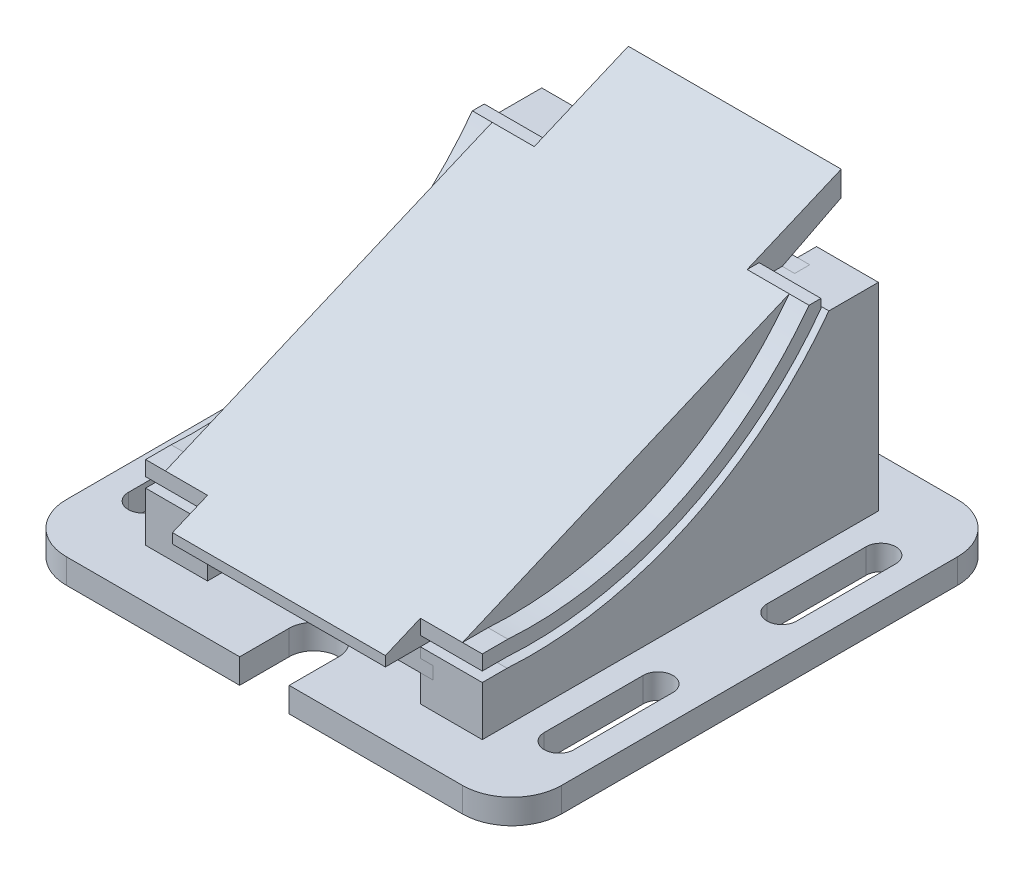
SolidWorks part; units mm, degrees
other "prensa"
other "base_prensa"
material "Aleación 1060"
ref_plane "Alzado" through (0, 0, 0) normal (0, 0, 1) x (1, 0, 0)
ref_plane "Planta" through (0, 0, 0) normal (0, 1, 0) x (1, 0, 0)
ref_plane "Vista lateral" through (0, 0, 0) normal (1, 0, 0) x (0, 0, -1)
sketch "Croquis2" plane through (0, 0, 0) normal (0, 1, 0) x (1, 0, 0)
  line L1 (50, -50) -> (-50, -50)
  line L2 (50, -50) -> (50, 50)
  line L3 (50, 50) -> (-50, 50)
  line L4 (-50, -50) -> (-50, 50)
  line L5 (50, -50) -> (-50, 50) construction
  line L6 (50, 50) -> (-50, -50) construction
  point P0 (0, 0)
  dimension "D1" = 100
  dimension "D2" = 100
extrude "Saliente-Extruir1" add sketch "Croquis2" along normal blind 5
fillet "Redondeo1" radius 10 4 edges at (-50, 2.5, -50) (50, 2.5, -50) (-50, 2.5, 50) (50, 2.5, 50)
sketch "Croquis3" plane through (0, 5, 0) normal (0, 1, 0) x (1, 0, 0)
  line L0 (-40, -50) -> (40, -50) construction
  line L1 (-5, -50) -> (5, -50)
  line L2 (-5, -50) -> (-5, -40)
  line L4 (5, -50) -> (5, -40)
  line L5 (-42, 32.5) -> (-42, 12.5) construction
  line L6 (-39, 32.5) -> (-39, 12.5)
  line L7 (-45, 32.5) -> (-45, 12.5)
  line L8 (42, 32.5) -> (42, 12.5) construction
  line L9 (45, 32.5) -> (45, 12.5)
  line L10 (39, 32.5) -> (39, 12.5)
  line L11 (-42, -12.5) -> (-42, -32.5) construction
  line L12 (-39, -12.5) -> (-39, -32.5)
  line L13 (-45, -12.5) -> (-45, -32.5)
  line L14 (42, -12.5) -> (42, -32.5) construction
  line L15 (45, -12.5) -> (45, -32.5)
  line L16 (39, -12.5) -> (39, -32.5)
  line L18 (-50, 40) -> (-50, -40) construction
  line L19 (50, -40) -> (50, 40) construction
  line L20 (0, 20.2073) -> (-17.5, 10.1036)
  line L21 (-17.5, 10.1036) -> (-17.5, -10.1036)
  line L22 (-17.5, -10.1036) -> (0, -20.2073)
  line L23 (0, -20.2073) -> (17.5, -10.1036)
  line L24 (17.5, -10.1036) -> (17.5, 10.1036)
  line L25 (17.5, 10.1036) -> (0, 20.2073)
  arc A0 (5, -40) -> (-5, -40) centre (0, -40) ccw
  arc A1 (-39, 32.5) -> (-45, 32.5) centre (-42, 32.5) ccw
  arc A2 (-45, 12.5) -> (-39, 12.5) centre (-42, 12.5) ccw
  arc A3 (45, 32.5) -> (39, 32.5) centre (42, 32.5) ccw
  arc A4 (39, 12.5) -> (45, 12.5) centre (42, 12.5) ccw
  arc A5 (-39, -12.5) -> (-45, -12.5) centre (-42, -12.5) ccw
  arc A6 (-45, -32.5) -> (-39, -32.5) centre (-42, -32.5) ccw
  arc A7 (45, -12.5) -> (39, -12.5) centre (42, -12.5) ccw
  arc A8 (39, -32.5) -> (45, -32.5) centre (42, -32.5) ccw
  circle A9 centre (0, 0) radius 17.5 construction
  point P10 (-42, 22.5)
  point P15 (42, 22.5)
  point P22 (-42, -22.5)
  point P29 (42, -22.5)
  dimension "D2" = 5
  dimension "D5" = 3
  dimension "D10" = 35
  dimension "D1" = 10
  dimension "D3" = 22.5
  dimension "D4" = 5
  dimension "D6" = 20
  dimension "D7" = 5
  dimension "D8" = 45
  dimension "D9" = 20
extrude "Cortar-Extruir1" cut sketch "Croquis3" against normal blind 5
sketch "Croquis4" plane through (0, 5, 0) normal (0, 1, 0) x (1, 0, 0)
  line L0 (-39, 12.5) -> (-39, 32.5) construction
  line L1 (-34, 40) -> (-24, 40)
  line L2 (-34, 40) -> (-34, -40)
  line L3 (-34, -40) -> (-24, -40)
  line L4 (-24, 40) -> (-24, -40)
  line L5 (24, 40) -> (34, 40)
  line L6 (24, 40) -> (24, -40)
  line L7 (24, -40) -> (34, -40)
  line L8 (34, 40) -> (34, -40)
  line L9 (39, 32.5) -> (39, 12.5) construction
  point P8 (-24, 0)
  point P10 (24, 0)
  dimension "D1" = 10
  dimension "D2" = 10
  dimension "D3" = 5
  dimension "D4" = 5
  dimension "D5" = 80
extrude "Saliente-Extruir2" add sketch "Croquis4" along normal blind 40
sketch "Croquis5" plane through (34, 0, 0) normal (1, 0, 0) x (0, 0, -1)
  line L1 (-40, 5) -> (40, 5) construction
  line L5 (-40, 15) -> (-35, 15)
  line L7 (-40, 45) -> (40, 45) construction
  line L8 (-40, 15) -> (-40, 45)
  line L9 (-40, 45) -> (30, 45)
  line L11 (40, 45) -> (40, 5) construction
  arc A0 (-35, 15) -> (30, 45) centre (-30.1189, 89.841) ccw
  dimension "D4" = 75
  dimension "D1" = 10
  dimension "D2" = 5
  dimension "D3" = 10
extrude "Cortar-Extruir2" cut sketch "Croquis5" against normal blind 84
sketch "Croquis8" plane through (-24, 0, 0) normal (1, 0, 0) x (0, 0, -1)
  line L0 (30, 45) -> (40, 45) construction
  line L1 (-40, 15) -> (-40, 5) construction
  line L2 (-40, 12.9735) -> (-40, 15)
  line L3 (33.0913, 45) -> (30, 45)
  line L5 (-40, 15) -> (-35, 15)
  arc A1 (-35, 15) -> (30, 45) centre (-30.1189, 89.841) ccw construction
  arc A2 (-35.1627, 12.5053) -> (32.004, 43.5053) centre (-30.1189, 89.841) ccw
  arc A3 (-40, 12.9735) -> (33.0913, 45) centre (-30.1189, 89.841) ccw
  arc A4 (-35, 15) -> (30, 45) centre (-30.1189, 89.841) ccw
  dimension "D1" = 2.5
extrude "Saliente-Extruir4" add sketch "Croquis8" along normal blind 2.5
sketch "Croquis9" plane through (-24, 0, 0) normal (1, 0, 0) x (0, 0, -1)
  line L1 (33.0913, 45) -> (40, 45) construction
  line L2 (-40, 12.9735) -> (-40, 5) construction
  line L3 (-40, 10.4536) -> (-40, 5)
  line L4 (-40, 5) -> (40, 5)
  line L5 (40, 5) -> (40, 45)
  line L6 (40, 45) -> (36.1328, 45)
  arc A2 (-40.3187, 10.4939) -> (35.1304, 43.5535) centre (-30.1189, 89.841) ccw
  arc A3 (-40, 10.4536) -> (36.1328, 45) centre (-30.1189, 89.841) ccw
  dimension "D1" = 2.5
extrude "Saliente-Extruir5" add sketch "Croquis9" along normal blind 2.5
mirror "Simetría1" about plane through (0, 0, 0) normal (1, 0, 0) of "Saliente-Extruir4", "Saliente-Extruir5"
sketch "Croquis10" plane through (0, 0, 0) normal (1, 0, 0) x (0, 0, -1)
  line L4 (-40, 20) -> (-34.8343, 20)
  line L5 (-40, 17) -> (-34.9344, 17)
  line L6 (-40, 17) -> (-34.9344, 17)
  line L7 (-40, 20) -> (-40, 17)
  line L8 (28.3968, 46.1958) -> (28.3968, 47.9894)
  line L9 (28.3968, 47.9894) -> (25.9921, 47.9894)
  arc A4 (-34.8343, 20) -> (25.9921, 47.9894) centre (-30.1189, 89.841) ccw
  arc A5 (-34.9344, 17) -> (28.3968, 46.1958) centre (-30.1189, 89.841) ccw
  arc A6 (-34.9344, 17) -> (28.3968, 46.1958) centre (-30.1189, 89.841) ccw
  dimension "D1" = 2
  dimension "D2" = 3
extrude "Saliente-Extruir6" add sketch "Croquis10" against normal up to vertex (34 mm away) and the other way up to vertex (34 mm away) separate body up to point (-34, 15, 35) other way up to point (34, 15, 35)
sketch "Croquis11" plane through (0, 0, 0) normal (1, 0, 0) x (0, 0, -1)
  line L0 (-40, 20) -> (25.9921, 47.9894)
  line L1 (-34.8343, 20) -> (-40, 20) construction
  line L2 (-34.8343, 20) -> (-40, 20)
  arc A0 (-34.8343, 20) -> (25.9921, 47.9894) centre (-30.1189, 89.841) ccw construction
  arc A1 (-34.8343, 20) -> (25.9921, 47.9894) centre (-30.1189, 89.841) ccw
extrude "Saliente-Extruir7" add sketch "Croquis11" along normal blind 30 and the other way blind 30
sketch "Croquis12" plane through (-24, 0, 0) normal (1, 0, 0) x (0, 0, -1)
  line L2 (36.1328, 45) -> (33.0913, 45)
  line L3 (-40, 12.9735) -> (-40, 10.4536)
  line L4 (36.1328, 45) -> (33.0913, 45)
  line L5 (-40, 12.9735) -> (-40, 10.4536)
  arc A2 (-40, 10.4536) -> (36.1328, 45) centre (-30.1189, 89.841) ccw
  arc A3 (-40, 12.9735) -> (33.0913, 45) centre (-30.1189, 89.841) ccw
  arc A4 (-40, 10.4536) -> (36.1328, 45) centre (-30.1189, 89.841) ccw
  arc A5 (-40, 12.9735) -> (33.0913, 45) centre (-30.1189, 89.841) ccw
  dimension "D1" = 0
extrude "Saliente-Extruir8" add sketch "Croquis12" along normal up to vertex (48 mm away) separate body up to point (24, 45, -36.1328)
sketch "Croquis15" plane through (0, 0, 0) normal (1, 0, 0) x (0, 0, -1)
  line L0 (-40, 17) -> (-34.9344, 17) construction
  line L1 (-40, 17) -> (-34.9344, 17)
  line L2 (-40, 12.9735) -> (-40, 17)
  line L3 (33.0913, 45) -> (33.0913, 46.1958)
  line L4 (33.0913, 46.1958) -> (28.3968, 46.1958)
  arc A0 (-40, 12.9735) -> (33.0913, 45) centre (-30.1189, 89.841) ccw construction
  arc A1 (-34.9344, 17) -> (28.3968, 46.1958) centre (-30.1189, 89.841) ccw construction
  arc A2 (-40, 12.9735) -> (33.0913, 45) centre (-30.1189, 89.841) ccw
  arc A3 (-34.9344, 17) -> (28.3968, 46.1958) centre (-30.1189, 89.841) ccw
extrude "Saliente-Extruir9" add sketch "Croquis15" along normal mid plane 43
sketch "Croquis16" plane through (0, 0, 0) normal (1, 0, 0) x (0, 0, -1)
  line L0 (-47.0733, 17) -> (44.9886, 56.0464)
  line L2 (25.9921, 47.9894) -> (-40, 20) construction
  line L3 (-40, 17) -> (-34.9344, 17) construction
  line L4 (-40, 17) -> (-34.9344, 17)
  line L5 (-40, 17) -> (-47.0733, 17)
  line L7 (28.3968, 46.1958) -> (33.0913, 46.1958)
  line L8 (33.0913, 46.1958) -> (44.9886, 56.0464)
  arc A0 (-34.9344, 17) -> (28.3968, 46.1958) centre (-30.1189, 89.841) ccw construction
  arc A1 (-34.9344, 17) -> (28.3968, 46.1958) centre (-30.1189, 89.841) ccw
  point P3 (-1.0424, 36.5232)
  dimension "D1" = 100
extrude "Saliente-Extruir10" add sketch "Croquis16" along normal mid plane 43
sketch "Croquis18" plane through (-21.5, 0, 0) normal (-1, 0, 0) x (0, 0, 1)
  line L0 (-44.9886, 56.0464) -> (-44.9886, 51.0464)
  line L1 (-44.9886, 51.0464) -> (-33.0913, 45)
  line L2 (-33.0913, 45) -> (-33.0913, 46.1958)
  line L3 (-33.0913, 46.1958) -> (-44.9886, 56.0464)
  line L4 (40, 15) -> (47.0733, 15)
  line L5 (47.0733, 15) -> (47.0733, 17)
  line L6 (47.0733, 17) -> (40, 17)
  line L7 (40, 17) -> (40, 15)
  point P10 (47.0733, 15)
  dimension "D1" = 5
extrude "Saliente-Extruir12" add sketch "Croquis18" against normal up to vertex (43 mm away) up to point (21.5, 56.0464, -44.9886)
